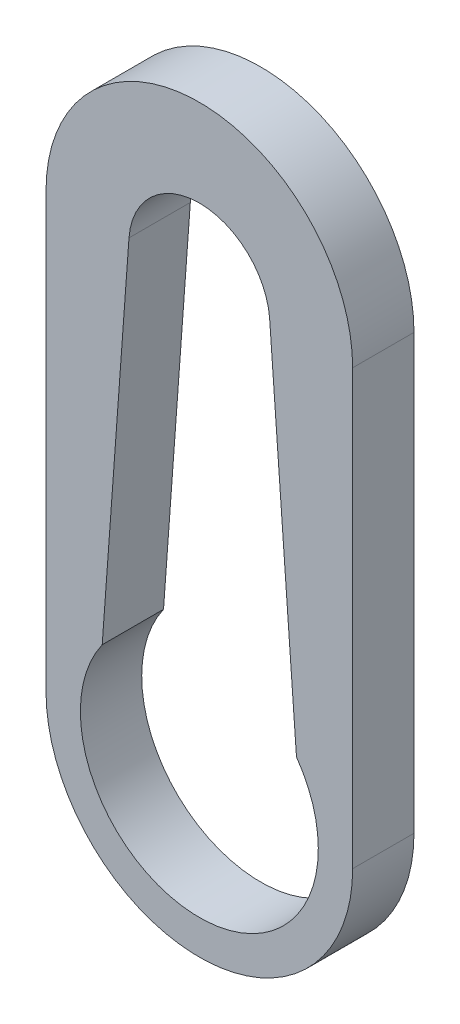
SolidWorks part; units mm, degrees
ref_plane "Front Plane" through (0, 0, 0) normal (0, 0, 1) x (1, 0, 0)
ref_plane "Top Plane" through (0, 0, 0) normal (0, 1, 0) x (1, 0, 0)
ref_plane "Right Plane" through (0, 0, 0) normal (1, 0, 0) x (0, 0, -1)
sketch "Sketch1" plane through (0, 0, 0) normal (0, 0, 1) x (1, 0, 0)
  line L0 (78.2916, 74.0996) -> (77.4175, 62.1716)
  line L1 (82.8793, 74.0996) -> (83.7534, 62.1716)
  line L3 (75.5854, 59.9315) -> (75.5854, 74.0776)
  line L5 (85.5854, 59.9315) -> (85.5854, 74.0776)
  arc A0 (75.5854, 74.0776) -> (85.5854, 74.0776) centre (80.5854, 74.0776) cw
  arc A1 (75.5854, 59.9315) -> (85.5854, 59.9315) centre (80.5854, 59.9315) ccw
  circle A2 centre (80.5854, 72.5315) radius 0.8
  circle A3 centre (80.5854, 59.9315) radius 1.85
  arc A5 (77.4175, 62.1716) -> (83.7534, 62.1716) centre (80.5854, 59.9324) ccw
  arc A6 (78.2916, 74.0996) -> (82.8793, 74.0996) centre (80.5854, 73.9315) cw
  point P21 (80.5854, 76.2315)
  point P23 (78.2916, 74.0996)
  point P26 (82.8793, 74.0996)
  point P27 (77.4175, 62.1716)
  point P28 (83.7534, 62.1716)
  point P29 (80.5854, 56.0529)
  point P30 (80.5854, 73.3315)
  dimension "D1" = 14.1462
  dimension "D2" = 10
  dimension "D4" = 2.9
extrude "Boss-Extrude1" add sketch "Sketch1" along normal blind 2 contours L3 A1 L5 A0 L0 A6 L1 A5 region at (75.8468, 67.0046, 0)
